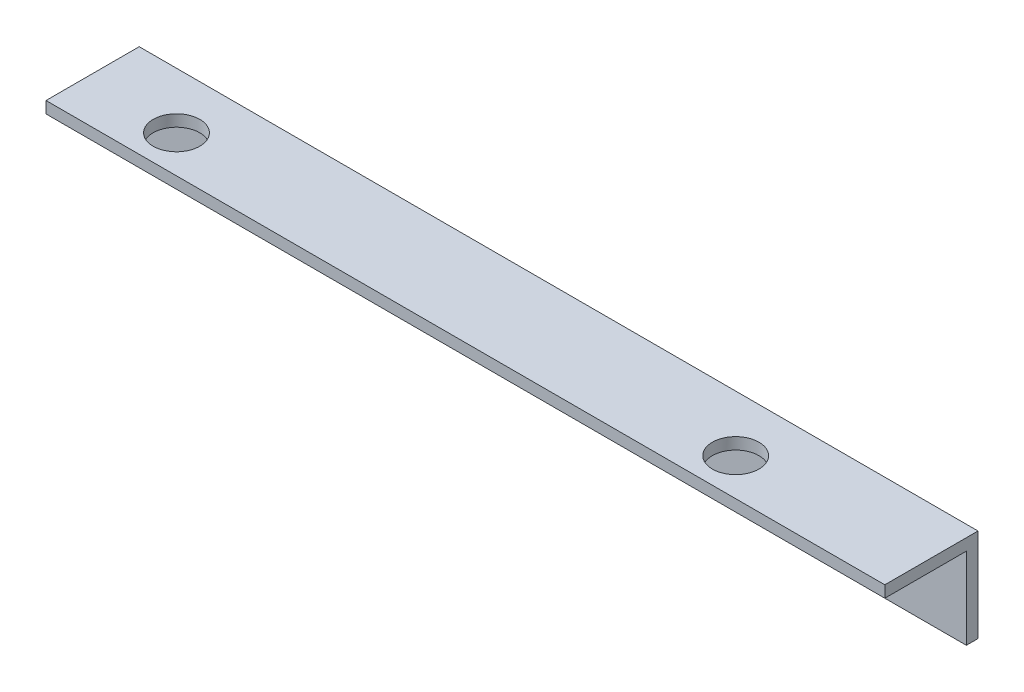
SolidWorks part; units mm, degrees
ref_plane "Front Plane" through (0, 0, 0) normal (0, 0, 1) x (1, 0, 0)
ref_plane "Top Plane" through (0, 0, 0) normal (0, 1, 0) x (1, 0, 0)
ref_plane "Right Plane" through (0, 0, 0) normal (1, 0, 0) x (0, 0, -1)
sketch "Sketch1" plane through (0, 0, 0) normal (1, 0, 0) x (0, 0, -1)
  line L0 (0, 0) -> (0, 12.7)
  line L1 (0, 55) -> (0, -55) construction
  line L11 (0, 12.7) -> (-12.7, 12.7)
  line L13 (-1.5875, 0) -> (-1.5875, 11.1125)
  line L14 (-1.5875, 11.1125) -> (-12.7, 11.1125)
  line L15 (-12.7, 11.1125) -> (-12.7, 12.7)
  line L16 (-1.5875, 0) -> (0, 0)
  point P7 (0, 0)
  dimension "D1" = 1.5875
  dimension "D2" = 12.7
  dimension "D3" = 11.1125
extrude "Boss-Extrude1" add sketch "Sketch1" along normal blind 57.15 and the other way blind 57.15
sketch "Sketch3" plane through (0, 0, 0) normal (0, 0, -1) x (-1, 0, 0)
  line L1 (-57.15, 0) -> (-57.15, 12.7) construction
  line L2 (31.75, 5.08) -> (-44.45, 5.08) construction
  line L3 (57.15, 12.7) -> (-57.15, 12.7) construction
  circle A0 centre (31.75, 5.08) radius 3.556
  circle A1 centre (-44.45, 5.08) radius 3.556
  dimension "D1" = 7.112
  dimension "D2" = 7.62
  dimension "D3" = 76.2
  dimension "D4" = 12.7
extrude "Cut-Extrude1" cut sketch "Sketch3" against normal through all
sketch "Sketch4" plane through (0, 12.7, 0) normal (0, 1, 0) x (1, 0, 0)
  line L2 (-44.45, -7.62) -> (31.75, -7.62) construction
  line L3 (-57.15, 0) -> (-57.15, -12.7) construction
  line L4 (-57.15, -12.7) -> (57.15, -12.7) construction
  circle A0 centre (-44.45, -7.62) radius 3.175
  circle A1 centre (31.75, -7.62) radius 3.175
  point P6 (0, 0)
  dimension "D1" = 6.35
  dimension "D2" = 76.2
  dimension "D3" = 12.7
  dimension "D4" = 5.08
extrude "Cut-Extrude2" cut sketch "Sketch4" against normal through all
